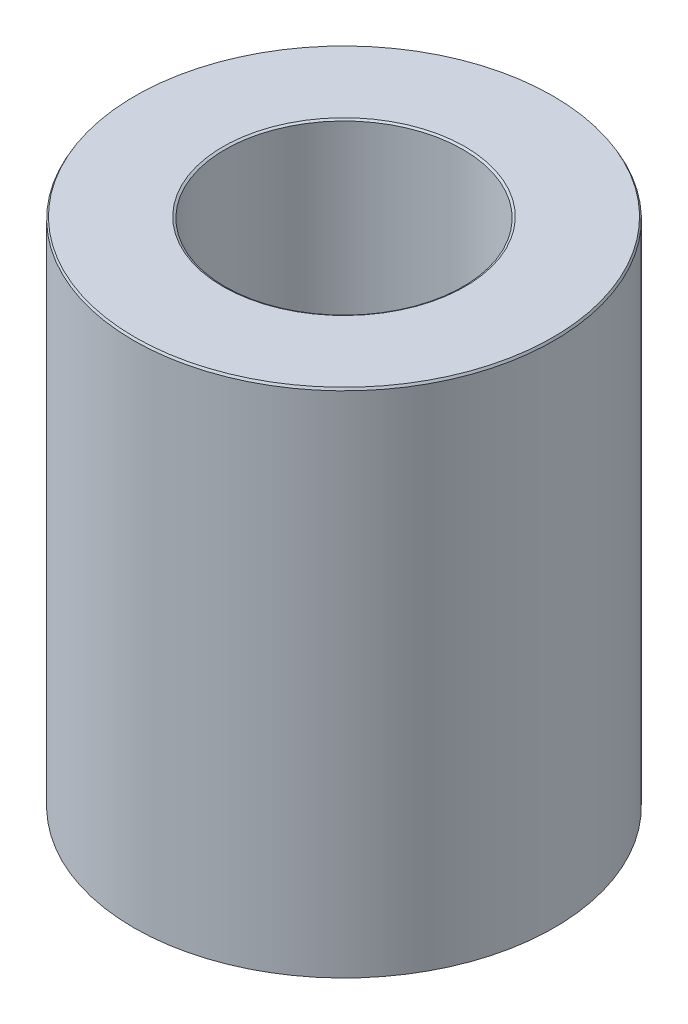
SolidWorks part; units mm, degrees
ref_plane "Front Plane" through (0, 0, 0) normal (0, 0, 1) x (1, 0, 0)
ref_plane "Top Plane" through (0, 0, 0) normal (0, 1, 0) x (1, 0, 0)
ref_plane "Right Plane" through (0, 0, 0) normal (1, 0, 0) x (0, 0, -1)
sketch "Sketch1" plane through (0, 0, 0) normal (0, 1, 0) x (1, 0, 0)
  circle A0 centre (0, 0) radius 50
  dimension "SLEEVE_OD" = 100
extrude "Boss-Extrude1" add sketch "Sketch1" along normal blind 121.7397
sketch "Sketch2" plane through (0, 0, 0) normal (0, 1, 0) x (1, 0, 0)
  circle A0 centre (0, 0) radius 28.2771
  dimension "BORE_D" = 56.5542
extrude "Cut-Extrude1" cut sketch "Sketch2" along normal through all
chamfer "Chamfer1" distance 0.523 angle 30 4 edges at (0, 121.7397, 28.2771) (0, 0, 28.2771) (0, 0, 50) (0, 121.7397, 50) first distance on face at (0, 121.7397, 28.2771) first distance on face at (0, 0, 28.2771) first distance on face at (0, 121.7397, 50)
